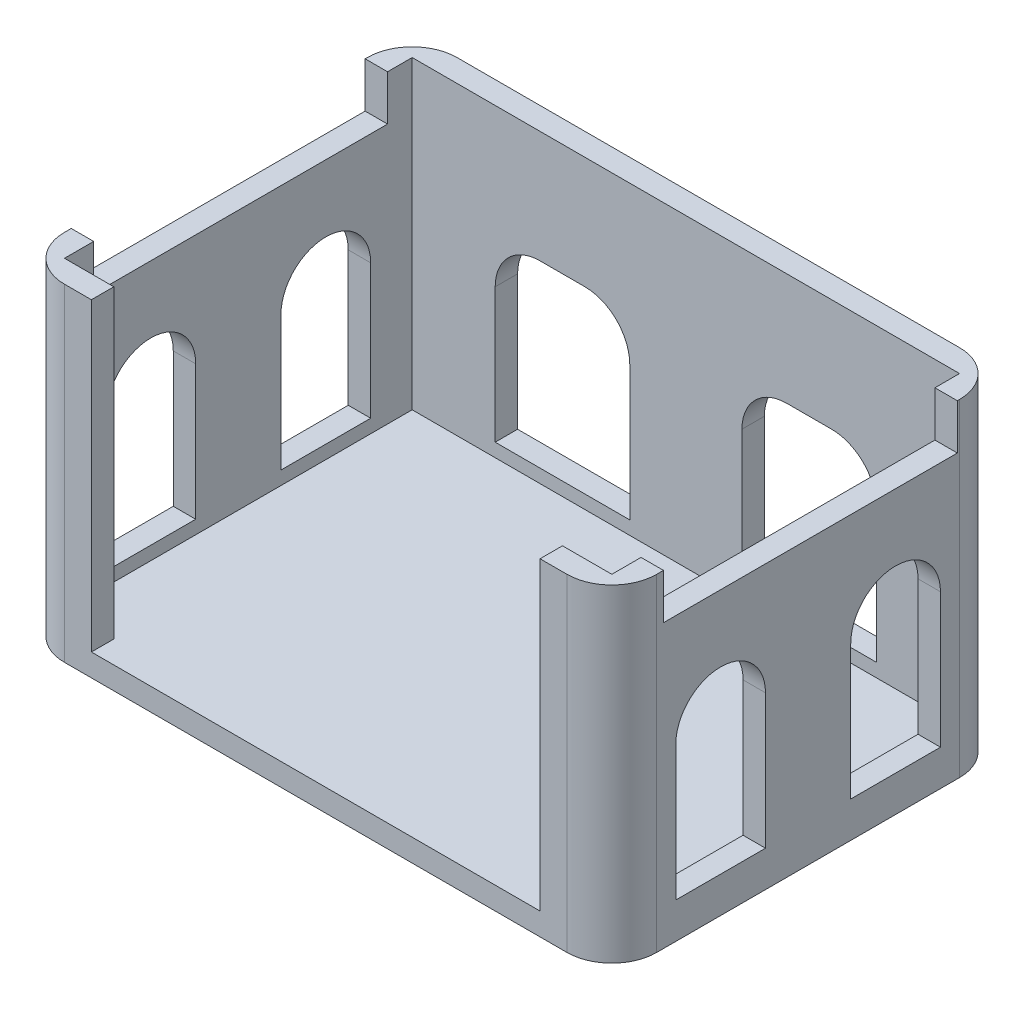
SolidWorks part; units mm, degrees
ref_plane "Front Plane" through (0, 0, 0) normal (0, 0, 1) x (1, 0, 0)
ref_plane "Top Plane" through (0, 0, 0) normal (0, 1, 0) x (1, 0, 0)
ref_plane "Right Plane" through (0, 0, 0) normal (1, 0, 0) x (0, 0, -1)
sketch "Sketch1" plane through (0, 0, 0) normal (0, 1, 0) x (1, 0, 0)
  line L1 (0, 0) -> (132, 0)
  line L2 (0, 0) -> (0, 87.5)
  line L3 (0, 87.5) -> (132, 87.5)
  line L4 (132, 0) -> (132, 87.5)
  dimension "D1" = 132
  dimension "D2" = 87.5
extrude "Boss-Extrude1" add sketch "Sketch1" along normal blind 5
sketch "Sketch2" plane through (0, 5, 0) normal (0, 1, 0) x (1, 0, 0)
  line L0 (0, 87.5) -> (0, 0) construction
  line L1 (5, 5) -> (16, 5)
  line L2 (5, 5) -> (5, 82.5)
  line L3 (5, 82.5) -> (127, 82.5)
  line L4 (127, 5) -> (127, 82.5)
  line L5 (132, 0) -> (132, 87.5) construction
  line L6 (132, 87.5) -> (0, 87.5) construction
  line L7 (0, 0) -> (132, 0) construction
  line L8 (16, 5) -> (16, 0)
  line L9 (0, 0) -> (16, 0)
  line L10 (0, 0) -> (0, 87.5)
  line L11 (0, 87.5) -> (132, 87.5)
  line L12 (132, 0) -> (132, 87.5)
  line L13 (116, 5) -> (116, 0)
  line L14 (116, 0) -> (132, 0)
  line L15 (116, 5) -> (127, 5)
  line L16 (0, 0) -> (16, -24.9583) construction
  line L17 (16, -24.9583) -> (16, 0) construction
  line L18 (132, 0) -> (116, -24.9583) construction
  line L19 (116, -24.9583) -> (116, 0) construction
  dimension "D1" = 5
  dimension "D2" = 5
  dimension "D3" = 5
  dimension "D4" = 5
  dimension "D5" = 100
extrude "Boss-Extrude2" add sketch "Sketch2" along normal blind 68
sketch "Sketch3" plane through (132, 0, 0) normal (1, 0, 0) x (0, 0, -1)
  line L0 (0, 28) -> (14.25, 28) construction
  line L1 (14.25, 48) -> (34.25, 48)
  line L2 (14.25, 48) -> (14.25, 8)
  line L3 (14.25, 8) -> (34.25, 8)
  line L4 (34.25, 48) -> (34.25, 8)
  line L5 (53.25, 48) -> (73.25, 48)
  line L6 (53.25, 48) -> (53.25, 8)
  line L7 (53.25, 8) -> (73.25, 8)
  line L8 (73.25, 48) -> (73.25, 8)
  line L9 (0, 73) -> (0, 0) construction
  line L10 (73.25, 28) -> (87.5, 28) construction
  line L11 (87.5, 73) -> (87.5, 0) construction
  line L12 (24.25, 48) -> (24.25, 73) construction
  line L13 (0, 73) -> (87.5, 73) construction
  dimension "D1" = 25
  dimension "D2" = 40
  dimension "D3" = 19
  dimension "D4" = 20
extrude "Cut-Extrude1" cut sketch "Sketch3" against normal through all and the other way through all
sketch "Sketch4" plane through (0, 0, -87.5) normal (0, 0, -1) x (-1, 0, 0)
  line L0 (-96.1035, 73) -> (-96.1035, 48) construction
  line L1 (-108.5, 48) -> (-78.5, 48)
  line L2 (-108.5, 48) -> (-108.5, 8)
  line L3 (-108.5, 8) -> (-78.5, 8)
  line L4 (-78.5, 48) -> (-78.5, 8)
  line L5 (-53.5, 48) -> (-23.5, 48)
  line L6 (-53.5, 48) -> (-53.5, 8)
  line L7 (-53.5, 8) -> (-23.5, 8)
  line L8 (-23.5, 48) -> (-23.5, 8)
  line L9 (-132, 73) -> (0, 73) construction
  line L10 (-132, 36.5) -> (-108.5, 36.5) construction
  line L11 (-132, 73) -> (-132, 0) construction
  line L12 (-23.5, 36.5) -> (0, 36.5) construction
  line L13 (0, 73) -> (0, 0) construction
  dimension "D1" = 25
  dimension "D2" = 40
  dimension "D3" = 25
  dimension "D4" = 30
extrude "Cut-Extrude2" cut sketch "Sketch4" against normal up to next
sketch "Sketch5" plane through (0, 0, 0) normal (-1, 0, 0) x (0, 0, 1)
  line L0 (-87.5, 73) -> (0, 73) construction
  line L1 (-77.0123, 73) -> (-11.5123, 73)
  line L2 (-77.0123, 73) -> (-77.0123, 62.9)
  line L3 (-77.0123, 62.9) -> (-11.5123, 62.9)
  line L4 (-11.5123, 73) -> (-11.5123, 62.9)
  line L5 (-87.5, 73) -> (-87.5, 0) construction
  dimension "D1" = 10.1
  dimension "D2" = 10.4877
  dimension "D3" = 65.5
extrude "Cut-Extrude3" cut sketch "Sketch5" against normal through all
fillet "Fillet1" radius 10 16 edges at (108.5, 48, -85) (78.5, 48, -85) (53.5, 48, -85) (23.5, 48, -85) (2.5, 48, -73.25) (2.5, 48, -53.25) (2.5, 48, -14.25) (2.5, 48, -34.25) (129.5, 48, -14.25) (129.5, 48, -34.25) (129.5, 48, -73.25) (129.5, 48, -53.25) (132, 36.5, -87.5) (132, 36.5, 0) (0, 36.5, 0) (0, 36.5, -87.5)
